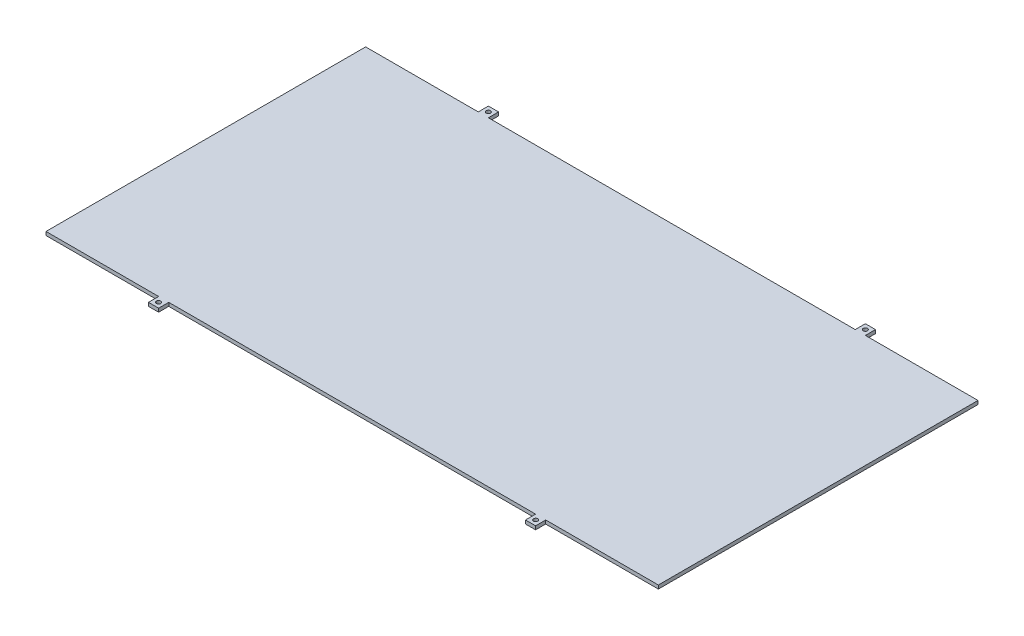
SolidWorks part; units mm, degrees
material "5052-H34"
ref_plane "Front Plane" through (0, 0, 0) normal (0, 0, 1) x (1, 0, 0)
ref_plane "Top Plane" through (0, 0, 0) normal (0, 1, 0) x (1, 0, 0)
ref_plane "Right Plane" through (0, 0, 0) normal (1, 0, 0) x (0, 0, -1)
sketch "Sketch1" plane through (0, 0, 0) normal (0, 0, 1) x (1, 0, 0)
  line L0 (-580.595, 2.8542) -> (-36.865, 2.8542)
  line L1 (-36.865, 2.8542) -> (-36.865, -0.3208)
  line L3 (-36.865, -0.3208) -> (-580.595, -0.3208)
  line L6 (-580.595, 2.8542) -> (-580.595, -0.3208)
  point P2 (-580.595, 2.8542)
  dimension "D1" = 3.175
  dimension "D2" = 543.73
  dimension "D3" = 36.865
  dimension "D4" = 2.8542
extrude "Boss-Extrude1" add sketch "Sketch1" along normal blind 283.825
sketch "GasketGroove" plane through (0, -0.3208, 0) normal (0, -1, 0) x (1, 0, 0)
  line L0 (-577.595, 279.825) -> (-577.595, 4)
  line L1 (-576.595, 3) -> (-40.865, 3)
  line L2 (-39.865, 4) -> (-39.865, 279.825)
  line L3 (-40.865, 280.825) -> (-576.595, 280.825)
  line L4 (-579.595, 282.825) -> (-579.595, 1) construction
  line L5 (-577.595, 282.825) -> (-577.595, 1) construction
  line L6 (-37.865, 280.825) -> (-579.595, 280.825) construction
  line L7 (-579.595, 3) -> (-37.865, 3) construction
  line L8 (-39.865, 1) -> (-39.865, 282.825) construction
  line L9 (-579.595, 1) -> (-37.865, 1) construction
  line L10 (-37.865, 282.825) -> (-579.595, 282.825) construction
  line L11 (-37.865, 1) -> (-37.865, 282.825) construction
  line L14 (-37.865, 1) -> (-37.865, 282.825)
  line L15 (-579.595, 1) -> (-37.865, 1)
  line L16 (-579.595, 282.825) -> (-579.595, 1)
  line L17 (-37.865, 282.825) -> (-579.595, 282.825)
  line L18 (-37.865, 2) -> (-37.865, 281.825)
  line L19 (-578.595, 1) -> (-38.865, 1)
  line L20 (-579.595, 281.825) -> (-579.595, 2)
  line L21 (-38.865, 282.825) -> (-578.595, 282.825)
  arc A0 (-579.595, 2) -> (-578.595, 1) centre (-578.595, 2) ccw
  arc A1 (-579.595, 281.825) -> (-578.595, 282.825) centre (-578.595, 281.825) cw
  arc A2 (-37.865, 281.825) -> (-38.865, 282.825) centre (-38.865, 281.825) ccw
  arc A3 (-38.865, 1) -> (-37.865, 2) centre (-38.865, 2) ccw
  arc A4 (-40.865, 3) -> (-39.865, 4) centre (-40.865, 4) ccw
  arc A5 (-576.595, 3) -> (-577.595, 4) centre (-576.595, 4) cw
  arc A6 (-576.595, 280.825) -> (-577.595, 279.825) centre (-576.595, 279.825) ccw
  arc A7 (-39.865, 279.825) -> (-40.865, 280.825) centre (-40.865, 279.825) ccw
  dimension "D6" = 1
  dimension "D7" = 1
  dimension "D8" = 1
  dimension "D9" = 1
  dimension "D10" = 1
  dimension "D11" = 1
  dimension "D12" = 1
  dimension "D13" = 1
  dimension "D1" = 1
  dimension "D2" = 2
  dimension "D3" = 2
  dimension "D4" = 2
  dimension "D5" = 2
extrude "Cut-Extrude1" cut sketch "GasketGroove" against normal blind 1.3
sketch "Sketch2" plane through (0, 2.8542, 0) normal (0, 1, 0) x (1, 0, 0)
  line L0 (-36.865, -283.825) -> (-580.595, -283.825) construction
  line L4 (-580.595, -283.825) -> (-580.595, 0) construction
  line L5 (-480.595, -283.825) -> (-471.595, -283.825)
  line L6 (-480.595, -283.825) -> (-480.595, -292.825)
  line L7 (-480.595, -292.825) -> (-471.595, -292.825)
  line L8 (-471.595, -283.825) -> (-471.595, -292.825)
  line L9 (-145.865, -283.825) -> (-136.865, -283.825)
  line L10 (-145.865, -283.825) -> (-145.865, -292.825)
  line L11 (-145.865, -292.825) -> (-136.865, -292.825)
  line L12 (-136.865, -283.825) -> (-136.865, -292.825)
  line L17 (-136.865, 0) -> (-145.865, 0)
  line L18 (-136.865, 0) -> (-136.865, 9)
  line L19 (-136.865, 9) -> (-145.865, 9)
  line L20 (-145.865, 0) -> (-145.865, 9)
  line L21 (-36.865, -283.825) -> (-36.865, 0) construction
  line L22 (-480.595, -288.325) -> (-471.595, -288.325) construction
  line L23 (-480.595, 0) -> (-471.595, 0)
  line L24 (-480.595, 0) -> (-480.595, 9)
  line L25 (-480.595, 9) -> (-471.595, 9)
  line L26 (-471.595, 0) -> (-471.595, 9)
  line L27 (-141.365, -292.825) -> (-141.365, -283.825) construction
  line L28 (-145.865, 4.5) -> (-136.865, 4.5) construction
  line L29 (-480.595, 4.5) -> (-471.595, 4.5) construction
  circle A0 centre (-476.095, -288.325) radius 1.925
  circle A1 centre (-141.365, -288.325) radius 1.925
  circle A2 centre (-141.365, 4.5) radius 1.925
  circle A3 centre (-476.095, 4.5) radius 1.925
  point P2 (-253.5028, -258.1424)
  dimension "D10" = 3.85
  dimension "D11" = 9
  dimension "D1" = 9
  dimension "D2" = 9
  dimension "D3" = 9
  dimension "D4" = 100
  dimension "D5" = 100
  dimension "D6" = 100
  dimension "D7" = 9
  dimension "D8" = 100
  dimension "D9" = 9
  dimension "D14" = 4.5
extrude "Boss-Extrude2" add sketch "Sketch2" against normal blind 3.125
